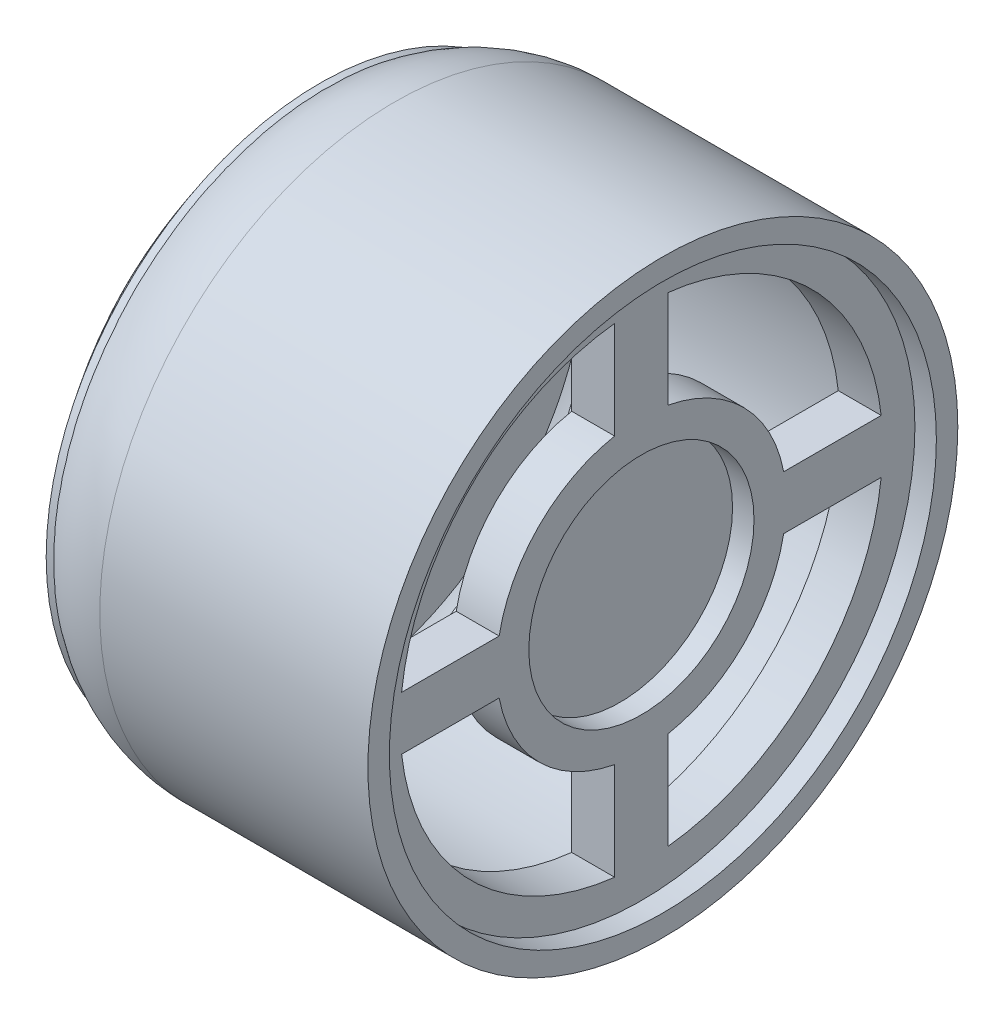
SolidWorks part; units mm, degrees
material "PLA"
ref_plane "Front Plane" through (0, 0, 0) normal (1, 0, 0) x (0, 1, 0)
ref_plane "Top Plane" through (0, 0, 0) normal (0, 0, 1) x (0, 1, 0)
ref_plane "Right Plane" through (0, 0, 0) normal (0, 1, 0) x (-1, 0, 0)
sketch "Sketch1" plane through (0, 0, 0) normal (1, 0, 0) x (0, 1, 0)
  line L0 (0, 6.5) -> (-20.5, 6.5)
  line L1 (0, 6.5) -> (0, -6.5)
  line L2 (0, -6.5) -> (-20.5, -6.5)
  line L3 (-20.5, 6.5) -> (-20.5, -6.5)
  line L4 (0, 0) -> (-24.2656, 0) construction
  line L5 (0, 6.5) -> (0, -6.5)
  line L6 (0, 19.7112) -> (0, -27.6906) construction
  line L7 (-16.5, 6.5) -> (7.5, 6.5)
  line L8 (-16.5, 6.5) -> (-16.5, -6.5)
  line L9 (-16.5, -6.5) -> (7.5, -6.5)
  line L10 (7.5, 6.5) -> (7.5, -6.5)
  circle A0 centre (0, 0) radius 10.25
  circle A1 centre (0, 0) radius 21.5058
  circle A3 centre (0, 0) radius 25.5058
  circle A4 centre (0, 0) radius 27.5058
  dimension "D1" = 20.5
  dimension "D2" = 20.5
  dimension "D3" = 13
  dimension "D4" = 24
  dimension "D5" = 7.5
  dimension "D6" = 4
  dimension "D7" = 2
extrude "Boss-Extrude1" add sketch "Sketch1" along normal blind 30 contours A4 A3 region at (0, -26.7278, 0)
sketch "Sketch2" plane through (30, 0, 0) normal (1, 0, 0) x (0, 1, 0)
  circle A0 centre (0, 0) radius 10.5
  circle A1 centre (0, 0) radius 27.5058
  circle A2 centre (0, 0) radius 27.5058
  circle M3 centre (0, 0) radius 25.5058
  circle M4 centre (0, 0) radius 27.5058
  dimension "D2" = 21
  dimension "D1" = 0
extrude "Boss-Extrude4" add sketch "Sketch2" along normal blind 6 contours M4 M3 region at (30, -26.7278, 0)
extrude "Boss-Extrude5" add sketch "Sketch2<4>" along normal blind 4 contours A0 M3 region at (30, -24.7844, 0)
sketch "Sketch2<4>" plane through (30, 0, 0) normal (1, 0, 0) x (0, 1, 0) same geometry as "Sketch2"
extrude "Boss-Extrude6" add sketch "Sketch2<5>" along normal blind 2 contours A0 region at (30, 0, 0)
sketch "Sketch2<5>" plane through (30, 0, 0) normal (1, 0, 0) x (0, 1, 0) same geometry as "Sketch2"
sketch "Sketch3" plane through (0, 0, 0) normal (-1, 0, 0) x (0, -1, 0)
  line L0 (0, 6.5) -> (-20.5, 6.5)
  line L1 (0, 6.5) -> (0, -6.5)
  line L2 (0, -6.5) -> (-20.5, -6.5)
  line L3 (-20.5, 6.5) -> (-20.5, -6.5)
  line L4 (0, 0) -> (27.3238, 0) construction
  line L5 (0, 6.5) -> (0, -6.5)
  line L6 (0, 25.2285) -> (0, -22.1733) construction
  line L7 (-16.5, 6.5) -> (7.5, 6.5)
  line L8 (-16.5, 6.5) -> (-16.5, -6.5)
  line L9 (-16.5, -6.5) -> (7.5, -6.5)
  line L10 (7.5, 6.5) -> (7.5, -6.5)
  circle A0 centre (0, 0) radius 12.5
  circle A1 centre (0, 0) radius 25.5058 construction
  circle A2 centre (0, 0) radius 27.5058 construction
  circle A3 centre (0, 0) radius 25.5058
  circle A4 centre (0, 0) radius 27.5058
  circle A5 centre (0, 0) radius 10.25
  circle A6 centre (0, 0) radius 21.5058
  circle A7 centre (51.6169, 6.4587) radius 23.5058
  circle M1 centre (0, 0) radius 25.5058
  dimension "D1" = 25
  dimension "D2" = 20.5
  dimension "D3" = 20.5
  dimension "D4" = 13
  dimension "D5" = 24
  dimension "D6" = 7.5
extrude "Boss-Extrude8" add sketch "Sketch3" against normal blind 4 contours L2 A6 L0 L7 A0 L9 | A6 M1 | L8 L0 L3 L2 | L3 A6 | A0 L7 L8 L9 | A5 L7 A0 L9 | A5 L9 A0 L7 region at (0, 18.5, 0) region at (0, 18.5, 7.1012) region at (0, 14.1742, 0) region at (0, 20.9031, 0) region at (0, -3.2833, 11.7074) region at (0, 10.6766, 0) region at (0, 24.7844, 0)
fillet "Fillet6" radius 11 1 edges at (0, 0, -27.5058)
sketch "Sketch8" plane through (34, 0, 0) normal (1, 0, 0) x (0, 1, 0)
  line L0 (-2.5, 22.3607) -> (-2.5, -22.3607)
  line L1 (2.5, 22.3607) -> (2.5, -22.3607)
  line L2 (-22.3607, 2.5) -> (22.3607, 2.5)
  line L3 (-22.3607, -2.5) -> (22.3607, -2.5)
  circle A0 centre (0, 0) radius 13.5
  circle A1 centre (0, 0) radius 22.5
  circle A2 centre (0, 0) radius 10.5 construction
  dimension "D1" = 3
  dimension "D2" = 9
  dimension "D3" = 5
extrude "Cut-Extrude3" cut sketch "Sketch8" against normal up to next contours L3 A1 L0 A0 | L0 A1 L2 A0 | L2 A1 L1 A0 | L1 A1 L3 A0 region at (34, -12.1516, 12.1516) region at (34, 12.1516, 12.1516) region at (34, -12.1516, -12.1516) region at (34, 12.1516, -12.1516)
